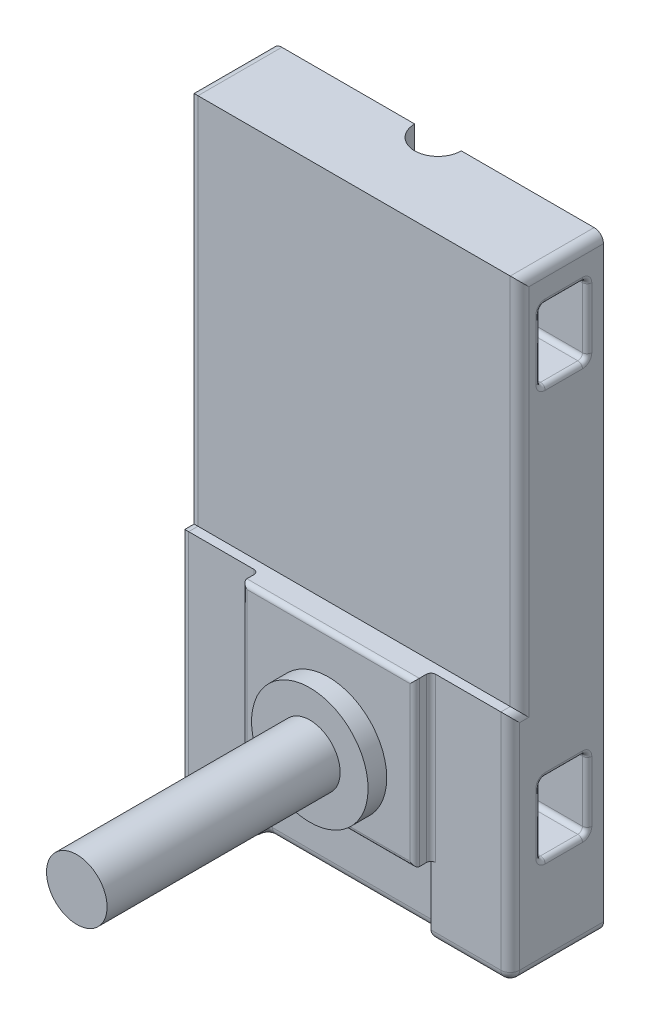
SolidWorks part; units mm, degrees
ref_plane "Front Plane" through (0, 0, 0) normal (0, 0, 1) x (1, 0, 0)
ref_plane "Top Plane" through (0, 0, 0) normal (0, 1, 0) x (1, 0, 0)
ref_plane "Right Plane" through (0, 0, 0) normal (1, 0, 0) x (0, 0, -1)
sketch "Sketch1" plane through (0, 0, 0) normal (0, 0, 1) x (1, 0, 0)
  line L1 (0, 0) -> (710, 0)
  line L2 (0, 0) -> (0, 1300)
  line L3 (0, 1300) -> (710, 1300)
  line L4 (710, 0) -> (710, 1300)
  dimension "D1" = 710
  dimension "D2" = 1300
extrude "Boss-Extrude1" add sketch "Sketch1" along normal blind 200
sketch "Sketch2" plane through (710, 0, 0) normal (1, 0, 0) x (0, 0, -1)
  line L0 (0, 0) -> (0, 1300) construction
  line L1 (-35, 200) -> (-135, 200)
  line L2 (-35, 200) -> (-35, 350)
  line L3 (-35, 350) -> (-135, 350)
  line L4 (-135, 200) -> (-135, 350)
  line L5 (-200, 0) -> (0, 0) construction
  line L6 (-35, 1080) -> (-135, 1080)
  line L7 (-35, 1080) -> (-35, 1230)
  line L8 (-35, 1230) -> (-135, 1230)
  line L9 (-135, 1080) -> (-135, 1230)
  line L10 (-200, 1300) -> (0, 1300) construction
  dimension "D1" = 100
  dimension "D2" = 150
  dimension "D3" = 100
  dimension "D4" = 150
  dimension "D5" = 200
  dimension "D6" = 70
  dimension "D7" = 35
  dimension "D8" = 35
extrude "Cut-Extrude1" cut sketch "Sketch2" against normal blind 988
sketch "Sketch4" plane through (0, 0, 0) normal (0, -1, 0) x (1, 0, 0)
  line L0 (0, 200) -> (710, 200) construction
  line L1 (170, 200) -> (540, 200)
  line L2 (170, 200) -> (170, 180)
  line L3 (170, 180) -> (540, 180)
  line L4 (540, 200) -> (540, 180)
  line L5 (0, 200) -> (0, 0) construction
  line L7 (710, 200) -> (710, 0) construction
  dimension "D1" = 20
  dimension "D2" = 170
  dimension "D3" = 170
extrude "Cut-Extrude2" cut sketch "Sketch4" against normal blind 150
sketch "Sketch5" plane through (0, 150, 0) normal (0, -1, 0) x (1, 0, 0)
  line L1 (170, 200) -> (540, 200)
  line L2 (170, 200) -> (170, 235)
  line L3 (170, 235) -> (540, 235)
  line L4 (540, 200) -> (540, 235)
  dimension "D1" = 35
extrude "Boss-Extrude2" add sketch "Sketch5" against normal blind 350
sketch "Sketch6" plane through (0, 0, 235) normal (0, 0, 1) x (1, 0, 0)
  line L0 (540, 150) -> (170, 150) construction
  line L1 (170, 150) -> (540, 150) construction
  circle A0 centre (355, 290) radius 125
  point P4 (355, 150)
  dimension "D1" = 250
  dimension "D2" = 140
extrude "Boss-Extrude3" add sketch "Sketch6" along normal blind 40
sketch "Sketch7" plane through (0, 0, 275) normal (0, 0, 1) x (1, 0, 0)
  circle A0 centre (355, 290) radius 65
  dimension "D1" = 130
extrude "Cut-Extrude3" cut sketch "Sketch7" against normal blind 126
fillet "Fillet4" radius 10 3 edges at (355, 150, 180) (540, 75, 180) (170, 75, 180)
fillet "Fillet5" radius 10 24 edges at (0, 1230, 85) (710, 1230, 85) (0, 1155, 135) (710, 1155, 135) (355, 1230, 135) (0, 1080, 85) (710, 1080, 85) (355, 1080, 135) (0, 275, 135) (710, 275, 135) (0, 275, 35) (710, 275, 35) (0, 350, 85) (355, 350, 135) (710, 350, 85) (355, 350, 35) (0, 200, 85) (355, 200, 35) (710, 200, 85) (355, 200, 135) (0, 1155, 35) (355, 1230, 35) (710, 1155, 35) (355, 1080, 35)
sketch "Sketch8" plane through (0, 1300, 0) normal (0, 1, 0) x (1, 0, 0)
  line L0 (180, -180) -> (530, -180) construction
  line L1 (0, -180) -> (710, -180)
  line L4 (710, 0) -> (0, 0)
  line L5 (0, 0) -> (0, -200)
  line L6 (0, -200) -> (710, -200)
  line L7 (710, -200) -> (710, 0)
  line L9 (0, -180) -> (0, -200)
  line L10 (0, -200) -> (710, -200)
  line L11 (710, -200) -> (710, 0)
  line M6 (0, 0) -> (0, -200)
  line M7 (0, -200) -> (710, -200)
  line M8 (710, -200) -> (710, 0)
  dimension "D1" = 0
extrude "Cut-Extrude6" cut sketch "Sketch8" against normal up to surface (800 mm away) contours L1 M6 M7 M8 region at (355, 1300, 190) up to face at (355, 500, 217.5)
sketch "Sketch9" plane through (0, 0, 0) normal (0, -1, 0) x (1, 0, 0)
  line L0 (0, 0) -> (710, 0) construction
  circle A0 centre (355, 0) radius 50
  dimension "D1" = 100
extrude "Cut-Extrude7" cut sketch "Sketch9" against normal blind 1563
fillet "Fillet6" radius 20 15 edges at (172.9289, 0, 182.9289) (537.0711, 0, 182.9289) (710, 900, 180) (710, 500, 190) (0, 500, 190) (0, 900, 180) (710, 250, 200) (0, 250, 200) (625, 0, 200) (85, 0, 200) (355, 0, 180) (710, 1300, 90) (0, 1300, 90) (0, 0, 100) (710, 0, 100)
fillet "Fillet7" radius 10 2 edges at (170, 325, 200) (540, 325, 200)
fillet "Fillet8" radius 10 4 edges at (355, 500, 235) (170, 325, 235) (355, 150, 235) (540, 325, 235)
sketch "Sketch10" plane through (0, 0, 275) normal (0, 0, 1) x (1, 0, 0)
  circle A0 centre (355, 290) radius 65 construction
  circle A1 centre (355, 290) radius 65
extrude "Boss-Extrude4" add sketch "Sketch10" along normal blind 500 separate body
